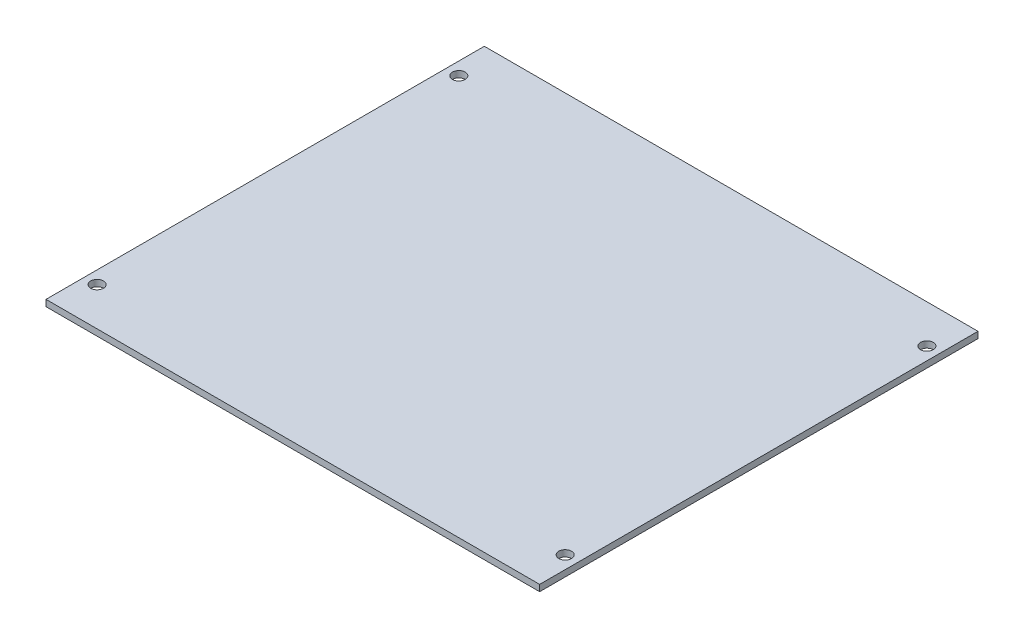
SolidWorks part; units mm, degrees
ref_plane "Спереди" through (0, 0, 0) normal (0, 0, 1) x (1, 0, 0)
ref_plane "Сверху" through (0, 0, 0) normal (0, 1, 0) x (1, 0, 0)
ref_plane "Справа" through (0, 0, 0) normal (1, 0, 0) x (0, 0, -1)
sketch "Эскиз1" plane through (0, 0, 0) normal (0, 1, 0) x (1, 0, 0)
  line L1 (-58, 51.5) -> (58, 51.5)
  line L2 (-58, 51.5) -> (-58, -51.5)
  line L3 (-58, -51.5) -> (58, -51.5)
  line L4 (58, 51.5) -> (58, -51.5)
  line L5 (-58, 51.5) -> (58, -51.5) construction
  line L6 (-58, -51.5) -> (58, 51.5) construction
  line L7 (-55, 42.5) -> (55, 42.5) construction
  line L8 (-55, 42.5) -> (-55, -42.5) construction
  line L9 (-55, -42.5) -> (55, -42.5) construction
  line L10 (55, 42.5) -> (55, -42.5) construction
  line L11 (-55, 42.5) -> (55, -42.5) construction
  line L12 (-55, -42.5) -> (55, 42.5) construction
  circle A0 centre (-55, 42.5) radius 1.5
  circle A1 centre (55, 42.5) radius 1.5
  circle A2 centre (55, -42.5) radius 1.5
  circle A3 centre (-55, -42.5) radius 1.5
  point P0 (0, 0)
  point P6 (0, 0)
  dimension "D5" = 3
  dimension "D1" = 116
  dimension "D2" = 103
  dimension "D3" = 110
  dimension "D4" = 85
extrude "Бобышка-Вытянуть1" add sketch "Эскиз1" along normal blind 1.5
